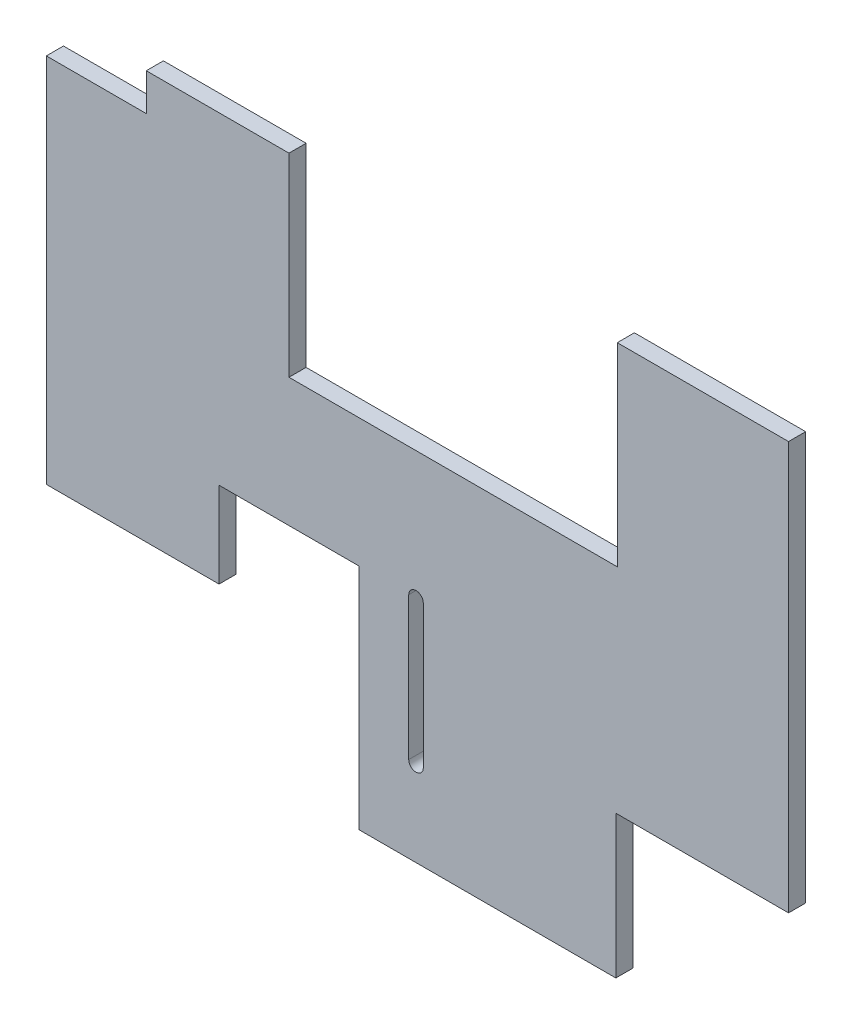
SolidWorks part; units mm, degrees
material "MDF"
ref_plane "Plano frontal" through (0, 0, 0) normal (0, 0, 1) x (1, 0, 0)
ref_plane "Plano superior" through (0, 0, 0) normal (0, 1, 0) x (1, 0, 0)
ref_plane "Plano direito" through (0, 0, 0) normal (1, 0, 0) x (0, 0, -1)
sketch "Esboço1" plane through (0, 0, 0) normal (0, 0, 1) x (1, 0, 0)
  line L0 (-45, 96.5) -> (-45, 28.5)
  line L1 (-130, -96.5) -> (130, -96.5)
  line L2 (-130, -96.5) -> (-130, 96.5)
  line L3 (-130, 96.5) -> (130, 96.5)
  line L4 (130, -96.5) -> (130, 96.5)
  line L5 (-130, -96.5) -> (130, 96.5) construction
  line L6 (-130, 96.5) -> (130, -96.5) construction
  line L7 (-45, 28.5) -> (70, 28.5)
  line L8 (-69.5, -16.5) -> (-20.5, -16.5)
  line L9 (-20.5, -16.5) -> (-20.5, -96.5)
  line L10 (0, 0) -> (0, 96.5) construction
  line L11 (69.5, -146.5) -> (69.5, -46.5)
  line L12 (69.5, -46.5) -> (130, -46.5)
  line L13 (70, 96.5) -> (70, 28.5)
  line L14 (-130, 83.5) -> (-95, 83.5)
  line L15 (-95, 83.5) -> (-95, 96.5)
  line L16 (-69.5, -16.5) -> (-69.5, -46.5)
  line L17 (-69.5, -46.5) -> (-130, -46.5)
  line L18 (-0.5, -66.5) -> (-0.5, -16.5) construction
  line L19 (-3.05, -66.5) -> (-3.05, -16.5)
  line L20 (2.05, -66.5) -> (2.05, -16.5)
  arc A0 (-3.05, -66.5) -> (2.05, -66.5) centre (-0.5, -66.5) ccw
  arc A1 (2.05, -16.5) -> (-3.05, -16.5) centre (-0.5, -16.5) ccw
  point P0 (0, 0)
  point P25 (-0.5, -41.5)
  dimension "D13" = 2.55
  dimension "D1" = 260
  dimension "D2" = 50
  dimension "D3" = 125
  dimension "D4" = 85
  dimension "D5" = 193
  dimension "D6" = 100
  dimension "D7" = 60.5
  dimension "D8" = 90
  dimension "D9" = 80
  dimension "D10" = 60
  dimension "D11" = 35
  dimension "D12" = 180
  dimension "D14" = 50
  dimension "D15" = 20
  dimension "D16" = 30
extrude "Ressalto-extrusão1" add sketch "Esboço1" along normal blind 6 contours L3 L7 L0 L2 L1 L11 L12 L4 region at (4.1054, 4.2889, 0)
